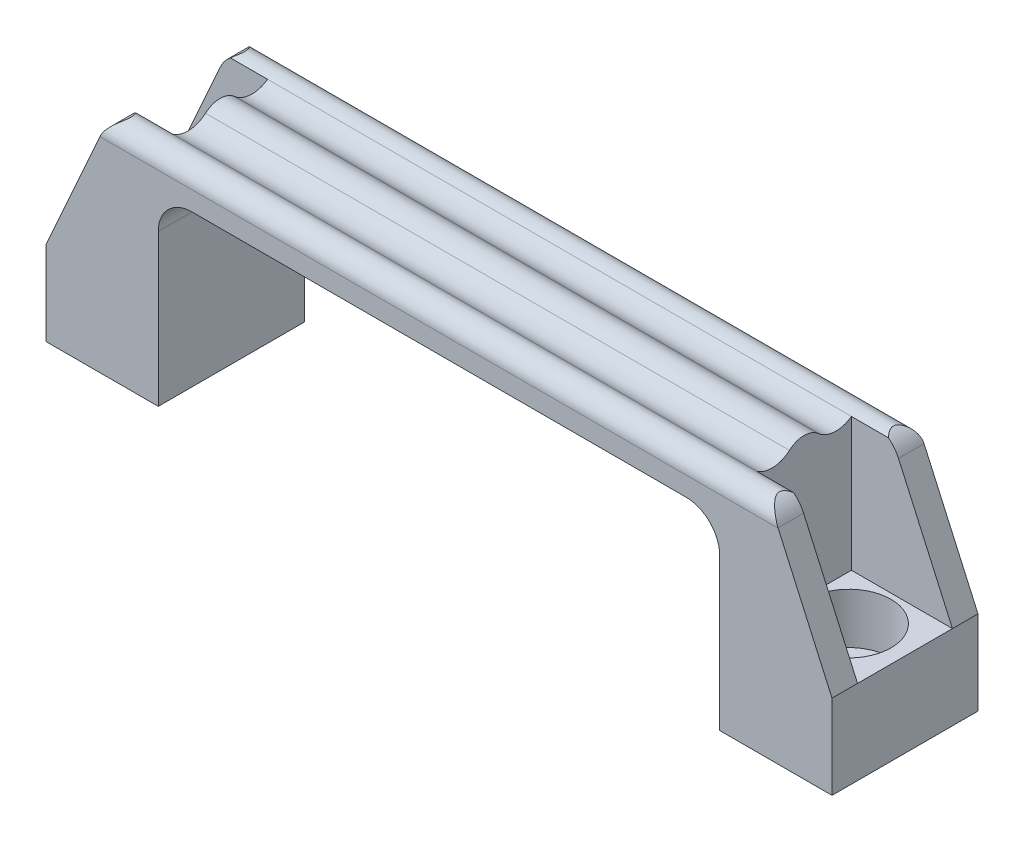
SolidWorks part; units mm, degrees
ref_plane "前视基准面" through (0, 0, 0) normal (0, 0, 1) x (1, 0, 0)
ref_plane "上视基准面" through (0, 0, 0) normal (0, 1, 0) x (1, 0, 0)
ref_plane "右视基准面" through (0, 0, 0) normal (1, 0, 0) x (0, 0, -1)
sketch "草图1" plane through (0, 0, 0) normal (0, 0, 1) x (1, 0, 0)
  line L20 (-70, 0) -> (70, 0) construction
  line L21 (-70, 0) -> (-70, 15)
  line L22 (-70, 15) -> (-58.8, 40)
  line L27 (-58.8, 40) -> (0, 40)
  line L30 (-60, 0) -> (-60, 15) construction
  line L31 (-67.5, 15) -> (-67.5, 6)
  line L32 (-67.5, 6) -> (-64.25, 6)
  line L33 (-64.25, 6) -> (-64.25, 0)
  line L34 (0, 0) -> (0, 22.8228) construction
  line L35 (-50, 0) -> (-50, 33)
  line L36 (-50, 33) -> (0, 33)
  point P5 (0, 0)
  point P16 (-67.5, 0)
  point P30 (-52.5, 0)
  point P32 (67.5, 0)
  point P33 (52.5, 0)
  dimension "D1" = 117.6
  dimension "L" = 140
  dimension "d" = 8.5
  dimension "h" = 40
  dimension "h2" = 15
  dimension "h1" = 9
  dimension "d1-" = 15
  dimension "A" = 120
  dimension "l1" = 100
  dimension "B" = 7
sketch "草图2" plane through (0, 0, 0) normal (1, 0, 0) x (0, 0, -1)
  line L0 (-13, 36.42) -> (-13, 0)
  line L1 (-13, 0) -> (13, 0)
  line L2 (13, 0) -> (13, 36.42)
  line L3 (0, 0) -> (0, 40) construction
  line L4 (0, 15) -> (0, 40) construction
  line L5 (0, 39.28) -> (-10.14, 39.28) construction
  line L6 (-13, 33) -> (13, 33)
  arc A0 (-2.5906, 39.0153) -> (2.5906, 39.0153) centre (0, 36.1) cw
  arc A1 (2.5906, 39.0153) -> (8.4556, 38.7314) centre (5.6993, 42.5136) ccw
  arc A2 (8.4556, 38.7314) -> (13, 36.42) centre (10.14, 36.42) cw
  arc A3 (-13, 36.42) -> (-8.4556, 38.7314) centre (-10.14, 36.42) cw
  arc A4 (-8.4556, 38.7314) -> (-2.5906, 39.0153) centre (-5.6993, 42.5136) ccw
  point P9 (0, 0)
  dimension "D2" = 2.86
  dimension "D3" = 4.68
  dimension "D4" = 3.9
  dimension "l" = 26
  dimension "D5" = 0.72
sketch "草图3" plane through (0, 0, 0) normal (0, 0, 1) x (1, 0, 0)
  line L0 (-70, 15) -> (-58.8, 40) construction
  line L1 (-70, 0) -> (-70, 15) construction
  line L2 (-50, 0) -> (-50, 33) construction
  line L3 (-70, 15) -> (-60.389, 36.4531)
  line L4 (-70, 0) -> (-70, 15)
  line L5 (-50, 0) -> (-50, 27)
  line L7 (44, 33) -> (-44, 33)
  line L8 (-70, 0) -> (-50, 0)
  line L9 (0, 0) -> (0, 11.4114) construction
  line L10 (0, 0) -> (0, 22.8228) construction
  line L11 (70, 0) -> (50, 0)
  line L13 (54.9134, 40) -> (-54.9134, 40)
  line L14 (50, 0) -> (50, 27)
  line L15 (70, 0) -> (70, 15)
  line L16 (70, 15) -> (60.389, 36.4531)
  arc A0 (-50, 27) -> (-44, 33) centre (-44, 27) cw
  arc A1 (-60.389, 36.4531) -> (-54.9134, 40) centre (-54.9134, 34) cw
  arc A2 (44, 33) -> (50, 27) centre (44, 27) cw
  arc A3 (54.9134, 40) -> (60.389, 36.4531) centre (54.9134, 34) cw
  point P23 (50, 33)
  point P26 (58.8, 40)
  dimension "D1" = 6
extrude "凸台-拉伸1" add sketch "草图3" against normal up to vertex (13 mm away) from vertex up to point (0, 0, -13) starting at point (0, 0, 13)
sketch "草图4" plane through (0, 0, 0) normal (1, 0, 0) x (0, 0, -1)
  line L0 (-13, 33) -> (13, 33) construction
  line L1 (-13, 33) -> (13, 33)
  line L2 (13, 36.42) -> (13, 33)
  line L3 (14, 33) -> (13, 33)
  line L4 (-13, 33) -> (-13, 36.42)
  line L5 (-14, 33) -> (-14, 41)
  line L6 (-14, 41) -> (14, 41)
  line L7 (14, 41) -> (14, 33)
  line L8 (-13, 33) -> (-14, 33)
  line L9 (0, 40) -> (0, 41) construction
  arc A0 (13, 36.42) -> (8.4556, 38.7314) centre (10.14, 36.42) ccw construction
  arc A1 (2.5906, 39.0153) -> (8.4556, 38.7314) centre (5.6993, 42.5136) ccw construction
  arc A2 (2.5906, 39.0153) -> (-2.5906, 39.0153) centre (0, 36.1) ccw construction
  arc A3 (-8.4556, 38.7314) -> (-2.5906, 39.0153) centre (-5.6993, 42.5136) ccw construction
  arc A4 (-8.4556, 38.7314) -> (-13, 36.42) centre (-10.14, 36.42) ccw construction
  arc A5 (13, 36.42) -> (8.4556, 38.7314) centre (10.14, 36.42) ccw
  arc A6 (2.5906, 39.0153) -> (8.4556, 38.7314) centre (5.6993, 42.5136) ccw
  arc A7 (2.5906, 39.0153) -> (-2.5906, 39.0153) centre (0, 36.1) ccw
  arc A8 (-8.4556, 38.7314) -> (-2.5906, 39.0153) centre (-5.6993, 42.5136) ccw
  arc A9 (-8.4556, 38.7314) -> (-13, 36.42) centre (-10.14, 36.42) ccw
  dimension "D1" = 1
extrude "切除-拉伸1" cut sketch "草图4" against normal up to vertex (70 mm away) and the other way up to vertex (70 mm away) contours L9 A7 A6 A5 L2 L3 L7 L6 | A7 L9 L6 L5 L8 L4 A9 A8 region at (0, 39.163, 8.279) region at (0, 39.163, -8.279) up to point (-70, 0, 0) other way up to point (70, 0, 0)
sketch "草图5" plane through (0, 0, 0) normal (0, 1, 0) x (1, 0, 0)
  line L0 (0, 0) -> (0, 12.9426) construction
  line L1 (-70, 8.45) -> (-52, 8.45)
  line L2 (-70, 8.45) -> (-70, -8.45)
  line L3 (-70, -8.45) -> (-52, -8.45)
  line L4 (-52, 8.45) -> (-52, -8.45)
  line L5 (-70, 13) -> (-70, -13) construction
  line L6 (-70, 0) -> (70, 0) construction
  line L7 (52, 8.45) -> (52, -8.45)
  line L8 (70, -8.45) -> (52, -8.45)
  line L9 (70, 8.45) -> (70, -8.45)
  line L10 (70, 8.45) -> (52, 8.45)
  line L11 (-70, 8.45) -> (-70, 13) construction
  line L12 (-52, 0) -> (-50, 0) construction
  line L13 (-50, 0) -> (0, 0) construction
  point P9 (-70, 0)
  dimension "D1" = 2
  dimension "D2" = 4.55
extrude "切除-拉伸2" cut sketch "草图5" along normal up to vertex (40 mm away) from vertex up to point (-58.8, 40, 0) starting at point (-70, 15, 0)
sketch "草图6" plane through (0, 0, 0) normal (0, 0, 1) x (1, 0, 0)
  line L0 (-60, 0) -> (-60, 17.9876) construction
  line L1 (-64.25, 0) -> (-64.25, 6)
  line L2 (-64.25, 6) -> (-67.5, 6)
  line L3 (-67.5, 6) -> (-67.5, 15)
  line L4 (-67.5, 15) -> (-60, 15)
  line L5 (-60, 15) -> (-60, 0)
  line L6 (-60, 0) -> (-64.25, 0)
revolve "切除-旋转1" cut sketch "草图6" angle 360 mid plane about L0
mirror "镜向1" about plane through (0, 0, 0) normal (1, 0, 0) of "切除-旋转1"
sketch "草图7" plane through (0, 0, 0) normal (1, 0, 0) x (0, 0, -1)
  line L0 (13, 0) -> (-13, 0) construction
  line L1 (9.29, 0) -> (7.61, 0)
  line L2 (9.29, 0) -> (9.29, 11.25)
  line L3 (9.29, 11.25) -> (7.61, 11.25)
  line L4 (7.61, 0) -> (7.61, 11.25)
  line L5 (-7.61, 0) -> (-9.29, 0)
  line L6 (-7.61, 0) -> (-7.61, 11.25)
  line L7 (-7.61, 11.25) -> (-9.29, 11.25)
  line L8 (-9.29, 0) -> (-9.29, 11.25)
  line L9 (0, 0) -> (0, 6.4331) construction
  point P8 (8.45, 0)
  point P9 (-8.45, 0)
  dimension "D2" = 1.68
  dimension "D3" = 11.25
extrude "切除-拉伸3" cut sketch "草图7" along normal up to vertex (67.5 mm away) from vertex up to point (67.5, 0, 0) starting at point (52.5, 0, 0)
extrude "切除-拉伸4" cut sketch "草图7<2>" along normal up to vertex (-52.5 mm away) from vertex up to point (-52.5, 0, 0) starting at point (-67.5, 0, 0)
sketch "草图7<2>" plane through (0, 0, 0) normal (1, 0, 0) x (0, 0, -1) same geometry as "草图7"
